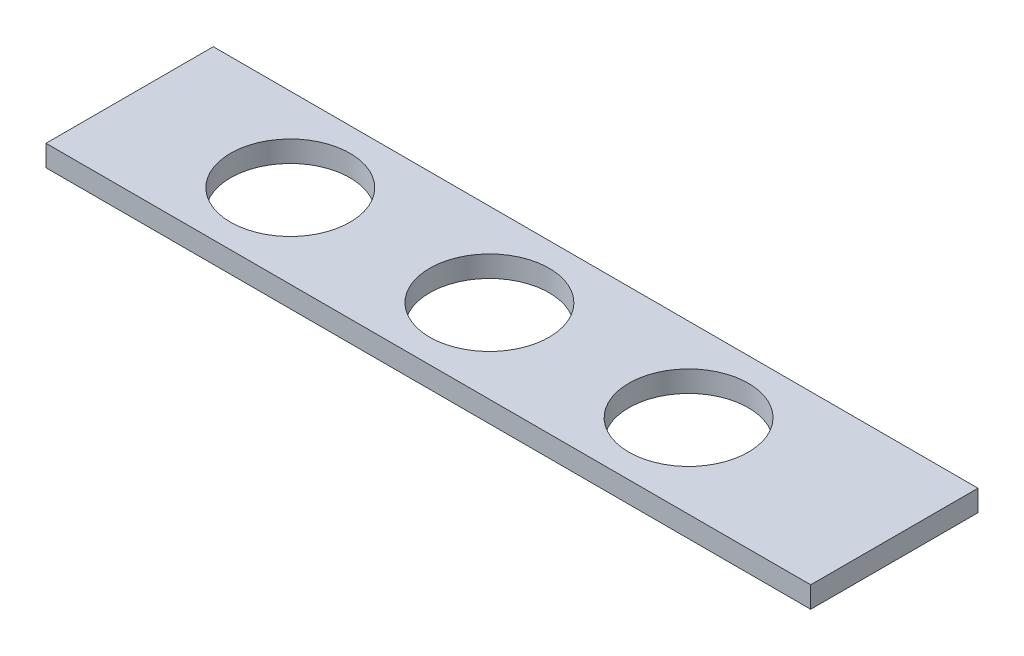
SolidWorks part; units mm, degrees
ref_plane "Front Plane" through (0, 0, 0) normal (0, 0, 1) x (1, 0, 0)
ref_plane "Top Plane" through (0, 0, 0) normal (0, 1, 0) x (1, 0, 0)
ref_plane "Right Plane" through (0, 0, 0) normal (1, 0, 0) x (0, 0, -1)
other "Configuration Table"
sketch "Эскиз1" plane through (0, 0, 0) normal (0, 1, 0) x (1, 0, 0)
  line L1 (0, 0) -> (288, 0)
  line L2 (0, 0) -> (0, 63)
  line L3 (0, 63) -> (288, 63)
  line L4 (288, 0) -> (288, 63)
extrude "Бобышка-Вытянуть1" add sketch "Эскиз1" along normal blind 8 contours L2 L1 L4 L3
sketch "Эскиз2" plane through (0, 8, 0) normal (0, 1, 0) x (1, 0, 0)
  line L3 (0, 0) -> (38, 0) construction
  line L4 (0, 0) -> (288, 0) construction
  line L5 (38, 0) -> (38, 63) construction
  line L6 (0, 63) -> (288, 63) construction
  line L7 (38, 0) -> (60.5, 0) construction
  line L8 (60.5, 0) -> (60.5, 63) construction
  line L9 (83, 63) -> (83, 0) construction
  line L10 (288, 0) -> (233, 0)
  line L11 (233, 0) -> (233, 63) construction
  line L12 (60.5, 31.5) -> (210.5, 31.5) construction
  circle A0 centre (60.5, 31.5) radius 22.5
  circle A1 centre (210.5, 31.5) radius 22.5
  circle A2 centre (135.5, 31.5) radius 22.5
  point P2 (0, 0)
  point P3 (142.6161, 69.5672)
  point P4 (138.2866, 68.5896)
  point P5 (135.5, 31.5)
  point P27 (144, 31.5)
  point P28 (0, 0)
extrude "Вырез-Вытянуть1" cut sketch "Эскиз2" against normal blind 8 contours A0
extrude "Вырез-Вытянуть2" cut sketch "Эскиз2<3>" against normal blind 8 contours A2
sketch "Эскиз2<3>" plane through (0, 8, 0) normal (0, 1, 0) x (1, 0, 0) same geometry as "Эскиз2"
extrude "Вырез-Вытянуть3" cut sketch "Эскиз2<4>" against normal blind 8 contours A1
sketch "Эскиз2<4>" plane through (0, 8, 0) normal (0, 1, 0) x (1, 0, 0) same geometry as "Эскиз2"
